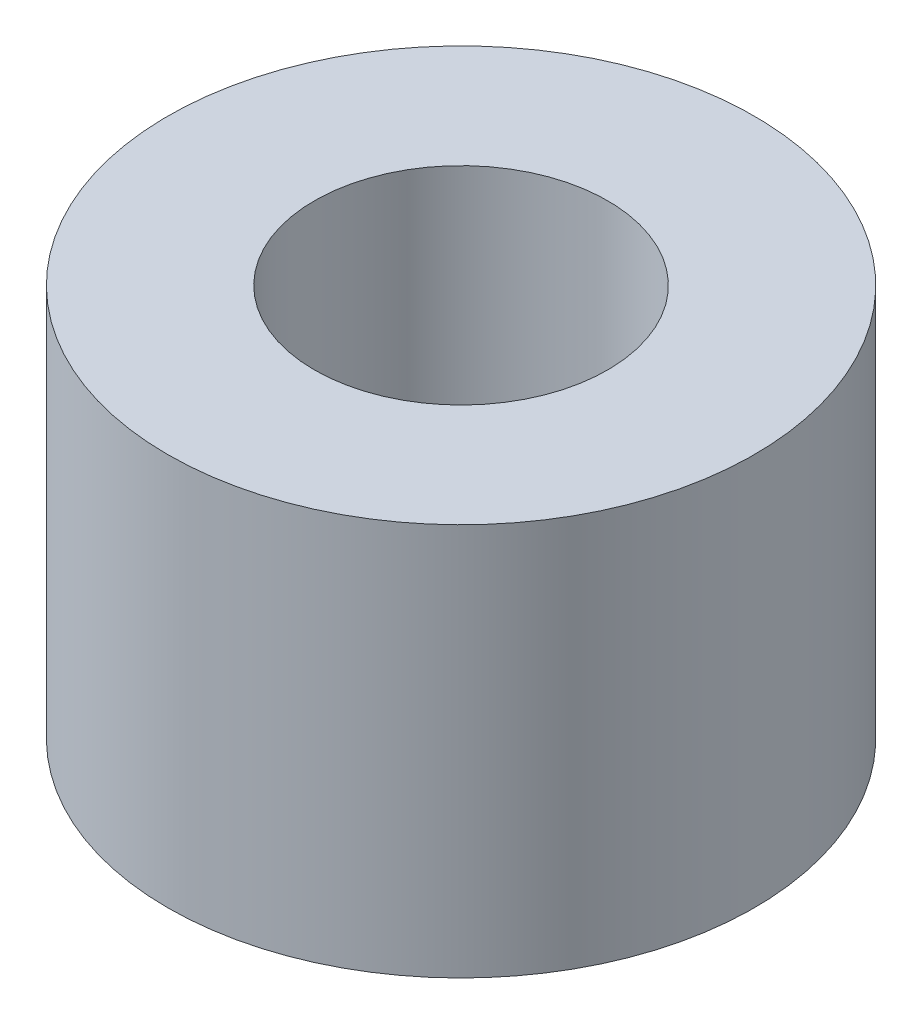
SolidWorks part; units mm, degrees
ref_plane "Front Plane" through (0, 0, 0) normal (0, 0, 1) x (1, 0, 0)
ref_plane "Top Plane" through (0, 0, 0) normal (0, 1, 0) x (1, 0, 0)
ref_plane "Right Plane" through (0, 0, 0) normal (1, 0, 0) x (0, 0, -1)
sketch "Sketch1" plane through (0, 0, 0) normal (0, 1, 0) x (1, 0, 0)
  circle A0 centre (0, 0) radius 6.35
  circle A1 centre (0, 0) radius 12.7
  dimension "D1" = 12.7
  dimension "D2" = 6.35
extrude "Boss-Extrude1" add sketch "Sketch1" along normal blind 17
